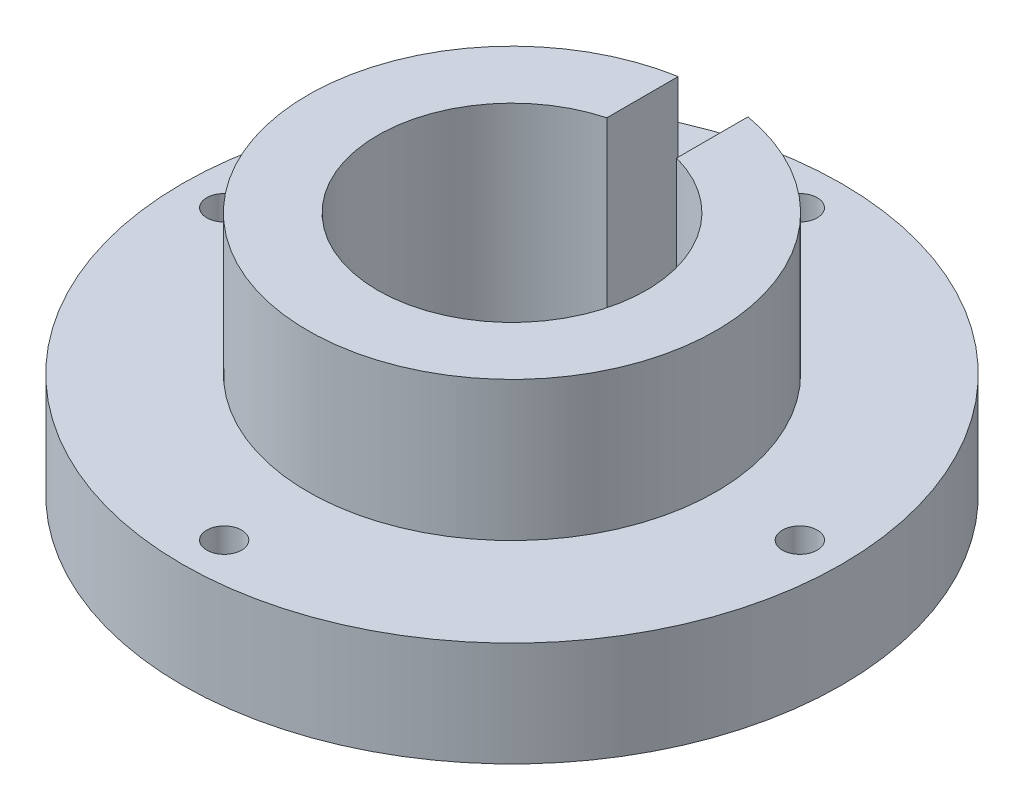
SolidWorks part; units mm, degrees
ref_plane "Front Plane" through (0, 0, 0) normal (0, 0, 1) x (1, 0, 0)
ref_plane "Top Plane" through (0, 0, 0) normal (0, 1, 0) x (1, 0, 0)
ref_plane "Right Plane" through (0, 0, 0) normal (1, 0, 0) x (0, 0, -1)
sketch "Sketch1" plane through (0, 0, 0) normal (0, 1, 0) x (1, 0, 0)
  line L0 (0, 0) -> (0, 60.4756) construction
  line L3 (-5, 18.5893) -> (-5, 29.25)
  line L4 (-5, 29.25) -> (5, 29.25)
  line L5 (5, 18.5893) -> (5, 29.25)
  circle A0 centre (0, 0) radius 47.25
  arc A1 (-5, 18.5893) -> (5, 18.5893) centre (0, 0) ccw
  circle A2 centre (0, 0) radius 41.25 construction
  circle A3 centre (0, 41.25) radius 2.5
  circle A4 centre (41.25, 0) radius 2.5
  circle A5 centre (0, -41.25) radius 2.5
  circle A6 centre (-41.25, 0) radius 2.5
  point P8 (0, 19.25)
  point P17 (0, 0)
  dimension "D1" = 94.5
  dimension "D2" = 38.5
  dimension "D3" = 82.5
  dimension "D4" = 5
  dimension "D6" = 10
  dimension "D7" = 10
  dimension "D5" = 4
extrude "Boss-Extrude1" add sketch "Sketch1" along normal blind 15
sketch "Sketch2" plane through (0, 15, 0) normal (0, 1, 0) x (1, 0, 0)
  line L0 (5, 18.5893) -> (5, 29.25) construction
  line L1 (-5, 29.25) -> (-5, 18.5893) construction
  line L2 (5, 18.5893) -> (5, 28.8195)
  line L3 (-5, 28.8195) -> (-5, 18.5893)
  arc A0 (-5, 28.8195) -> (5, 28.8195) centre (0, 0) ccw
  arc A1 (-5, 18.5893) -> (5, 18.5893) centre (0, 0) ccw construction
  arc A2 (-5, 18.5893) -> (5, 18.5893) centre (0, 0) ccw
  dimension "D1" = 58.5
extrude "Boss-Extrude2" add sketch "Sketch2" along normal blind 20
